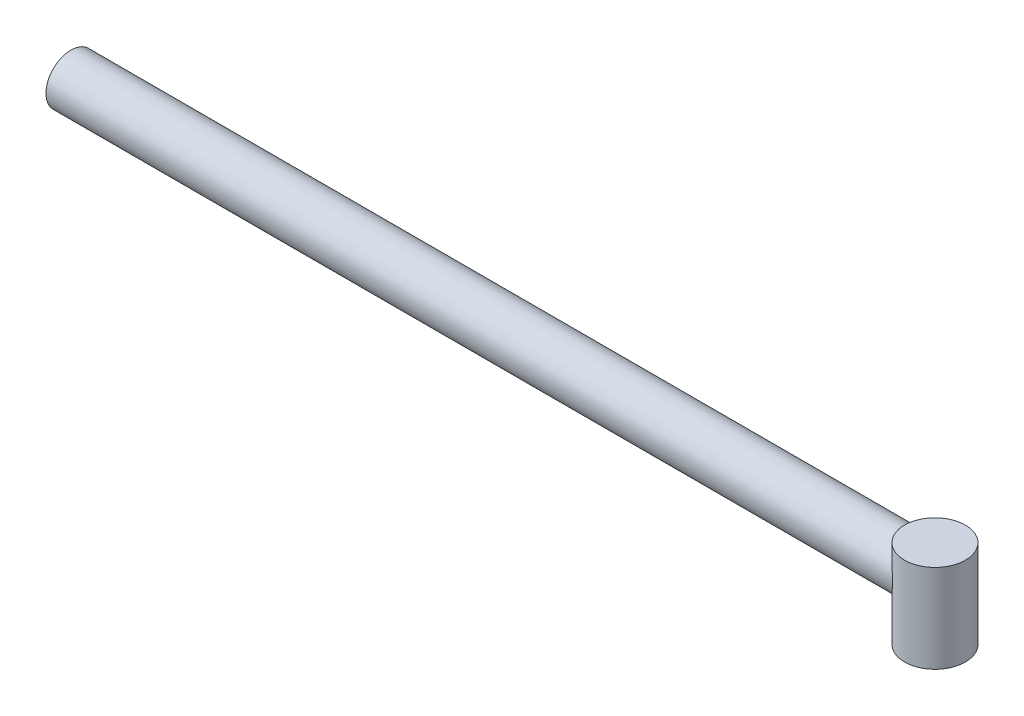
SolidWorks part; units mm, degrees
ref_plane "Front Plane" through (0, 0, 0) normal (0, 0, 1) x (1, 0, 0)
ref_plane "Top Plane" through (0, 0, 0) normal (0, 1, 0) x (1, 0, 0)
ref_plane "Right Plane" through (0, 0, 0) normal (1, 0, 0) x (0, 0, -1)
sketch "Base Sketch" plane through (0, 0, 0) normal (0, 1, 0) x (1, 0, 0)
  circle A0 centre (-6.4, 65) radius 5
extrude "Base" add sketch "Base Sketch" along normal blind 14.5 from offset 36.5
ref_axis "Engine Axis" through (5.95, 0, 0) along (-1, 0, 0)
sketch "Whip Sketch" plane through (0, 0, 0) normal (1, 0, 0) x (0, 0, -1)
  circle A0 centre (65, 46) radius 4.1
extrude "Whip" add sketch "Whip Sketch" against normal blind 142 from offset 6.4 offset against normal yes
